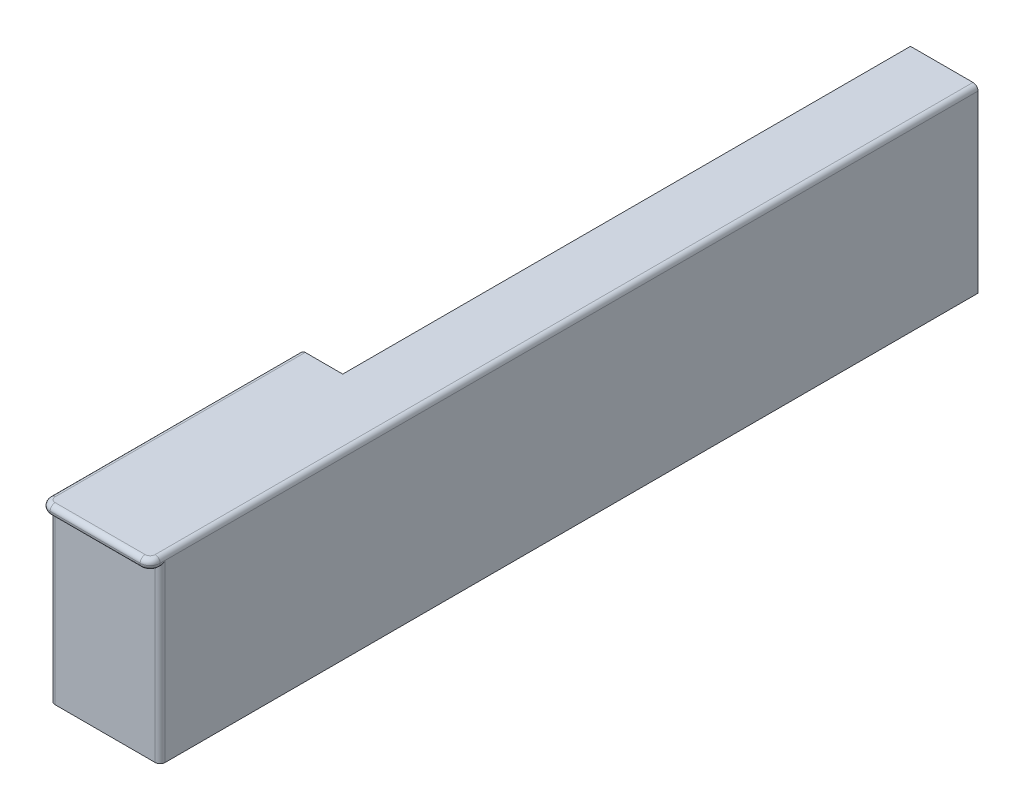
SolidWorks part; units mm, degrees
ref_plane "Front Plane" through (0, 0, 0) normal (0, 0, 1) x (1, 0, 0)
ref_plane "Top Plane" through (0, 0, 0) normal (0, 1, 0) x (1, 0, 0)
ref_plane "Right Plane" through (0, 0, 0) normal (1, 0, 0) x (0, 0, -1)
sketch "Sketch1" plane through (0, 0, 0) normal (0, 1, 0) x (1, 0, 0)
  line L1 (-11, -81.75) -> (11, -81.75)
  line L2 (-11, -81.75) -> (-11, 81.75)
  line L3 (-11, 81.75) -> (11, 81.75)
  line L4 (11, -81.75) -> (11, 81.75)
  line L5 (-11, -81.75) -> (11, 81.75) construction
  line L6 (-11, 81.75) -> (11, -81.75) construction
  point P0 (0, 0)
  dimension "D1" = 163.5
  dimension "D2" = 22
extrude "Boss-Extrude1" add sketch "Sketch1" along normal blind 36 contours L2 L3 L4 L1
fillet "Fillet1" radius 1 2 edges at (-11, 18, 81.75) (11, 18, 81.75)
sketch "Sketch2" plane through (0, 36, 0) normal (0, 1, 0) x (1, 0, 0)
  line L0 (11, -80.75) -> (11, 81.75) construction
  line L1 (-11, 81.75) -> (11, 81.75)
  line L2 (-11, 81.75) -> (-11, -83.75)
  line L3 (-11, -83.75) -> (11, -83.75)
  line L4 (11, 81.75) -> (11, -83.75)
  line L5 (-10, -81.75) -> (10, -81.75) construction
  dimension "D1" = 2
extrude "Boss-Extrude2" add sketch "Sketch2" against normal blind 2
fillet "Fillet2" radius 2 2 edges at (-11, 35, 83.75) (11, 35, 83.75)
fillet "Fillet3" radius 1 10 edges at (-11, 34, 81.25) (-10.4142, 34, 83.1642) (11, 34, 81.25) (10.4142, 34, 83.1642) (11, 36, 0) (10.4142, 36, 83.1642) (0, 36, 83.75) (-10.4142, 36, 83.1642) (-11, 36, 0) (0, 34, 83.75)
sketch "Sketch3" plane through (0, 36, 0) normal (0, 1, 0) x (1, 0, 0)
  line L1 (7.5, -31.75) -> (11, -31.75)
  line L2 (7.5, -31.75) -> (7.5, 81.75)
  line L3 (7.5, 81.75) -> (11, 81.75)
  line L4 (11, -31.75) -> (11, 81.75)
  line L5 (7.5, -31.75) -> (11, 81.75) construction
  line L6 (7.5, 81.75) -> (11, -31.75) construction
  line L7 (-10, -81.75) -> (10, -81.75) construction
  line L8 (-11, 81.75) -> (11, 81.75) construction
  line L9 (11, 81.75) -> (11, -80.75) construction
  dimension "D1" = 3.5
  dimension "D2" = 50
extrude "Cut-Extrude2" [suppressed] cut sketch "Sketch3" against normal through all
sketch "Sketch5" plane through (-11, 0, 0) normal (-1, 0, 0) x (0, 0, 1)
  line L0 (81.75, 34) -> (81.75, 0) construction
  line L1 (80.75, 0) -> (-81.75, 0) construction
  line L2 (-81.75, 36) -> (81.75, 36) construction
  line L3 (-81.75, 35) -> (-81.75, 0) construction
  line L8 (31.75, 36) -> (-81.75, 36)
  line L9 (31.75, 0) -> (31.75, 36)
  line L10 (-81.75, 0) -> (31.75, 0)
  line L11 (-81.75, 36) -> (-81.75, 0)
  dimension "D1" = 50
extrude "Cut-Extrude4" [suppressed] cut sketch "Sketch5" against normal blind 3.5
sketch "Sketch4" [suppressed] plane through (7.5, 0, 0) normal (1, 0, 0) x (0, 0, -1)
  line L4 (81.75, 36) -> (-31.75, 36)
  line L5 (-31.75, 36) -> (-31.75, 0)
  line L6 (-31.75, 0) -> (81.75, 0)
  line L7 (81.75, 0) -> (81.75, 36)
  line L8 (81.75, 36) -> (-31.75, 36)
  line L9 (-31.75, 36) -> (-31.75, 0)
  line L10 (-31.75, 0) -> (81.75, 0)
  line L11 (81.75, 0) -> (81.75, 36)
  dimension "D1" = 0
extrude "Cut-Extrude3" [suppressed] cut sketch "Sketch4" against normal blind 3.25
sketch "Sketch6" [suppressed] plane through (-7.5, 0, 0) normal (-1, 0, 0) x (0, 0, 1)
  line L4 (-81.75, 36) -> (-81.75, 0)
  line L5 (-81.75, 0) -> (31.75, 0)
  line L6 (31.75, 0) -> (31.75, 36)
  line L7 (31.75, 36) -> (-81.75, 36)
  line L8 (-81.75, 36) -> (-81.75, 0)
  line L9 (-81.75, 0) -> (31.75, 0)
  line L10 (31.75, 0) -> (31.75, 36)
  line L11 (31.75, 36) -> (-81.75, 36)
  dimension "D1" = 0
extrude "Cut-Extrude5" [suppressed] cut sketch "Sketch6" against normal blind 3.25
sketch "White" plane through (0, 0, 0) normal (0, 1, 0) x (1, 0, 0)
  line L0 (12.5, -81.75) -> (34.5, -81.75)
  line L1 (-11, -81.75) -> (11, -81.75)
  line L2 (-11, -81.75) -> (-11, 81.75)
  line L3 (-11, 81.75) -> (11, 81.75)
  line L4 (11, -81.75) -> (11, 81.75)
  line L5 (12.5, -81.75) -> (12.5, 81.75)
  line L6 (12.5, 81.75) -> (34.5, 81.75)
  line L7 (34.5, -81.75) -> (34.5, 81.75)
  line L8 (36, -81.75) -> (58, -81.75)
  line L9 (36, -81.75) -> (36, 81.75)
  line L10 (36, 81.75) -> (58, 81.75)
  line L11 (58, -81.75) -> (58, 81.75)
  line L12 (59.5, -81.75) -> (81.5, -81.75)
  line L13 (59.5, -81.75) -> (59.5, 81.75)
  line L14 (59.5, 81.75) -> (81.5, 81.75)
  line L15 (81.5, -81.75) -> (81.5, 81.75)
  line L16 (83, -81.75) -> (105, -81.75)
  line L17 (83, -81.75) -> (83, 81.75)
  line L18 (83, 81.75) -> (105, 81.75)
  line L19 (105, -81.75) -> (105, 81.75)
  line L20 (106.5, -81.75) -> (128.5, -81.75)
  line L21 (106.5, -81.75) -> (106.5, 81.75)
  line L22 (106.5, 81.75) -> (128.5, 81.75)
  line L23 (128.5, -81.75) -> (128.5, 81.75)
  line L24 (130, -81.75) -> (152, -81.75)
  line L25 (130, -81.75) -> (130, 81.75)
  line L26 (130, 81.75) -> (152, 81.75)
  line L27 (152, -81.75) -> (152, 81.75)
  dimension "D1" = 7
sketch "Black" plane through (0, 0, 0) normal (0, 1, 0) x (1, 0, 0)
  line L0 (-11, 81.75) -> (11, 81.75) construction
  line L1 (16, -31.75) -> (4, -31.75)
  line L2 (16, -31.75) -> (16, 81.75)
  line L3 (16, 81.75) -> (4, 81.75)
  line L4 (4, -31.75) -> (4, 81.75)
  line L6 (31, -31.75) -> (43, -31.75)
  line L7 (31, -31.75) -> (31, 81.75)
  line L8 (31, 81.75) -> (43, 81.75)
  line L9 (43, -31.75) -> (43, 81.75)
  line L10 (12.5, -81.75) -> (34.5, -81.75) construction
  line L11 (16, -31.75) -> (31, -31.75) construction
  line L12 (36, 81.75) -> (58, 81.75) construction
  line L13 (106.5, 81.75) -> (128.5, 81.75) construction
  line L14 (111.75, 81.75) -> (99.75, 81.75)
  line L15 (111.75, 81.75) -> (111.75, -31.75)
  line L16 (111.75, -31.75) -> (99.75, -31.75)
  line L17 (99.75, 81.75) -> (99.75, -31.75)
  line L18 (83, 81.75) -> (105, 81.75) construction
  line L19 (126.75, 81.75) -> (138.75, 81.75)
  line L20 (126.75, 81.75) -> (126.75, -31.75)
  line L21 (126.75, -31.75) -> (138.75, -31.75)
  line L22 (138.75, 81.75) -> (138.75, -31.75)
  line L23 (84.75, 81.75) -> (72.75, 81.75)
  line L24 (84.75, 81.75) -> (84.75, -31.75)
  line L25 (84.75, -31.75) -> (72.75, -31.75)
  line L26 (72.75, 81.75) -> (72.75, -31.75)
  line L27 (105, -81.75) -> (106.5, -81.75) construction
  point P14 (23.5, -81.75)
  point P15 (23.5, -31.75)
  point P36 (105.75, -81.75)
  point P37 (105.75, -31.75)
  dimension "D1" = 50
  dimension "D2" = 12
  dimension "D3" = 12
  dimension "D4" = 15
  dimension "D5" = 15
  dimension "D6" = 15
sketch "Sketch11" plane through (0, 36, 0) normal (0, 1, 0) x (1, 0, 0)
  line L1 (11, 81.75) -> (2.5, 81.75)
  line L2 (11, 81.75) -> (11, -31.75)
  line L3 (11, -31.75) -> (2.5, -31.75)
  line L4 (2.5, 81.75) -> (2.5, -31.75)
  line L5 (16, -31.75) -> (4, -31.75) construction
  dimension "D1" = 8.5
extrude "C" [suppressed] cut sketch "Sketch11" against normal through all
sketch "Sketch12" plane through (0, 36, 0) normal (0, 1, 0) x (1, 0, 0)
  line L0 (31, -31.75) -> (43, -31.75) construction
  line L1 (-11, 81.75) -> (-6, 81.75)
  line L2 (-11, 81.75) -> (-11, -31.75)
  line L3 (-11, -31.75) -> (-6, -31.75)
  line L4 (-6, 81.75) -> (-6, -31.75)
  line L5 (11, 81.75) -> (6, 81.75)
  line L6 (11, 81.75) -> (11, -31.75)
  line L7 (11, -31.75) -> (6, -31.75)
  line L8 (6, 81.75) -> (6, -31.75)
  dimension "D1" = 5
  dimension "D2" = 5
extrude "D" [suppressed] cut sketch "Sketch12" against normal through all
sketch "Sketch13" plane through (0, 36, 0) normal (0, 1, 0) x (1, 0, 0)
  line L1 (-11, 81.75) -> (-2.5, 81.75)
  line L2 (-11, 81.75) -> (-11, -31.75)
  line L3 (-11, -31.75) -> (-2.5, -31.75)
  line L4 (-2.5, 81.75) -> (-2.5, -31.75)
  line L5 (16, -31.75) -> (4, -31.75) construction
  dimension "D1" = 8.5
extrude "E" cut sketch "Sketch13" against normal through all
sketch "Sketch14" plane through (0, 36, 0) normal (0, 1, 0) x (1, 0, 0)
  line L0 (16, -31.75) -> (4, -31.75) construction
  line L1 (11, 81.75) -> (0.75, 81.75)
  line L2 (11, 81.75) -> (11, -31.75)
  line L3 (11, -31.75) -> (0.75, -31.75)
  line L4 (0.75, 81.75) -> (0.75, -31.75)
  dimension "D1" = 10.25
extrude "F" [suppressed] cut sketch "Sketch14" against normal through all
sketch "Sketch15" plane through (0, 36, 0) normal (0, 1, 0) x (1, 0, 0)
  line L1 (-11, 81.75) -> (-7.75, 81.75)
  line L2 (-11, 81.75) -> (-11, -31.75)
  line L3 (-11, -31.75) -> (-7.75, -31.75)
  line L4 (-7.75, 81.75) -> (-7.75, -31.75)
  line L5 (11, 81.75) -> (4.25, 81.75)
  line L6 (11, 81.75) -> (11, -31.75)
  line L7 (11, -31.75) -> (4.25, -31.75)
  line L8 (4.25, 81.75) -> (4.25, -31.75)
  line L9 (16, -31.75) -> (4, -31.75) construction
  dimension "D1" = 3.25
  dimension "D2" = 6.75
extrude "G" [suppressed] cut sketch "Sketch15" against normal through all
sketch "Sketch16" plane through (0, 36, 0) normal (0, 1, 0) x (1, 0, 0)
  line L0 (16, -31.75) -> (4, -31.75) construction
  line L1 (-11, 81.75) -> (-4.25, 81.75)
  line L2 (-11, 81.75) -> (-11, -31.75)
  line L3 (-11, -31.75) -> (-4.25, -31.75)
  line L4 (-4.25, 81.75) -> (-4.25, -31.75)
  line L5 (11, 81.75) -> (7.75, 81.75)
  line L6 (11, 81.75) -> (11, -31.75)
  line L7 (11, -31.75) -> (7.75, -31.75)
  line L8 (7.75, 81.75) -> (7.75, -31.75)
  dimension "D1" = 6.75
  dimension "D2" = 3.25
extrude "A" [suppressed] cut sketch "Sketch16" against normal through all
sketch "Sketch17" plane through (0, 36, 0) normal (0, 1, 0) x (1, 0, 0)
  line L0 (16, -31.75) -> (4, -31.75) construction
  line L1 (-11, 81.75) -> (-0.75, 81.75)
  line L2 (-11, 81.75) -> (-11, -31.75)
  line L3 (-11, -31.75) -> (-0.75, -31.75)
  line L4 (-0.75, 81.75) -> (-0.75, -31.75)
  dimension "D1" = 10.25
extrude "B" [suppressed] cut sketch "Sketch17" against normal through all
